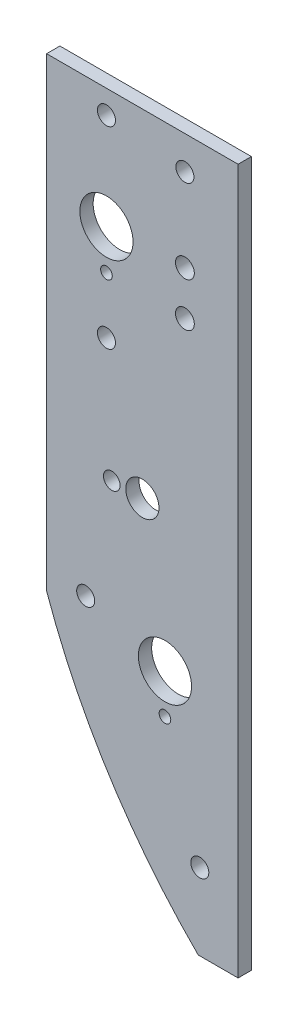
SolidWorks part; units mm, degrees
material "Acrylic (Medium-high impact)"
ref_plane "Front Plane" through (0, 0, 0) normal (0, 0, 1) x (1, 0, 0)
ref_plane "Top Plane" through (0, 0, 0) normal (0, 1, 0) x (1, 0, 0)
ref_plane "Right Plane" through (0, 0, 0) normal (1, 0, 0) x (0, 0, -1)
sketch "Sketch1" plane through (0, 0, 0) normal (0, 0, 1) x (1, 0, 0)
  line L4 (-45.72, 26.9875) -> (-45.72, -84.1375)
  line L5 (-9.525, -141.2875) -> (0, -141.2875)
  line L6 (0, -141.2875) -> (0, 26.9875)
  line L7 (0, 26.9875) -> (-45.72, 26.9875)
  line L8 (-45.72, 26.9875) -> (-45.72, -84.1375)
  line L9 (-9.525, -141.2875) -> (0, -141.2875)
  line L10 (0, -141.2875) -> (0, 26.9875)
  line L11 (0, 26.9875) -> (-45.72, 26.9875)
  arc A1 (-45.72, -84.1375) -> (-9.525, -141.2875) centre (97.9169, -33.2042) ccw
  arc A2 (-45.72, -84.1375) -> (-9.525, -141.2875) centre (97.9169, -33.2042) ccw
  dimension "D1" = 0
extrude "Boss-Extrude1" add sketch "Sketch1" against normal blind 3.175
hole_wizard "1/2 (0.5) Diameter Hole1" positions "Sketch4" profile "Sketch3" hole size "1/2" standard "ANSI Inch" end condition through all
sketch "Sketch4" plane through (0, 0, 0) normal (0, 0, 1) x (1, 0, 0)
  point P0 (-17.4625, -86.5505)
  point P4 (-31.4325, -1.6203)
sketch "Sketch3" plane through (-17.4625, -86.5505, 0) normal (1, 0, 0) x (0, -1, 0)
  line L0 (0, 0) -> (0, 3.175)
  line L1 (0, 3.175) -> (6.35, 3.175)
  line L2 (6.35, 3.175) -> (6.35, 0)
  line L5 (6.35, 0) -> (0, 0)
  line L11 (0, -6.35) -> (0, 107.95) construction
  dimension "Thru Hole Dia." = 12.7
  dimension "Thru Hole Depth" = 3.175
hole_wizard "5/16 (0.3125) Diameter Hole1" positions "Sketch6" profile "Sketch5" hole size "5/16" standard "ANSI Inch" end condition through all
sketch "Sketch6" plane through (0, 0, 0) normal (0, 0, 1) x (1, 0, 0)
  point P0 (-22.86, -53.5305)
sketch "Sketch5" plane through (-22.86, -53.5305, 0) normal (1, 0, 0) x (0, -1, 0)
  line L0 (0, 0) -> (0, 3.175)
  line L1 (0, 3.175) -> (3.9687, 3.175)
  line L2 (3.9687, 3.175) -> (3.9687, 0)
  line L5 (3.9687, 0) -> (0, 0)
  line L11 (0, -6.35) -> (0, 107.95) construction
  dimension "Thru Hole Dia." = 7.9375
  dimension "Thru Hole Depth" = 3.175
hole_wizard "5/32 (0.15625) Diameter Hole1" positions "Sketch8" profile "Sketch7" hole size "5/32" standard "ANSI Inch" end condition through all
sketch "Sketch8" plane through (0, 0, 0) normal (0, 0, 1) x (1, 0, 0)
  line L0 (-22.86, -49.5617) -> (-22.86, -53.5305) construction
  circle A0 centre (-22.86, -53.5305) radius 3.9688 construction
  point P11 (-30.1611, -53.5305)
sketch "Sketch7" plane through (-30.1611, -53.5305, 0) normal (1, 0, 0) x (0, -1, 0)
  line L0 (0, 0) -> (0, 3.175)
  line L1 (0, 3.175) -> (1.9844, 3.175)
  line L2 (1.9844, 3.175) -> (1.9844, 0)
  line L5 (1.9844, 0) -> (0, 0)
  line L11 (0, -6.35) -> (0, 107.95) construction
  dimension "Thru Hole Dia." = 3.9688
  dimension "Thru Hole Depth" = 3.175
hole_wizard "7/64 (0.10938) Diameter Hole1" positions "Sketch10" profile "Sketch9" hole size "7/64" standard "ANSI Inch" end condition through all
sketch "Sketch10" plane through (0, 0, 0) normal (0, 0, 1) x (1, 0, 0)
  point P0 (-17.4646, -95.9667)
  point P3 (-31.4325, -11.1589)
sketch "Sketch9" plane through (-17.4646, -95.9667, 0) normal (1, 0, 0) x (0, -1, 0)
  line L0 (0, 0) -> (0, 3.175)
  line L1 (0, 3.175) -> (1.3891, 3.175)
  line L2 (1.3891, 3.175) -> (1.3891, 0)
  line L5 (1.3891, 0) -> (0, 0)
  line L11 (0, -6.35) -> (0, 107.95) construction
  dimension "Thru Hole Dia." = 2.7783
  dimension "Thru Hole Depth" = 3.175
sketch "Sketch11" plane through (0, 0, -3.175) normal (0, 0, -1) x (-1, 0, 0)
  line L5 (19.8437, -15.24) -> (19.8437, 3.175)
  line L6 (19.8437, 3.175) -> (8.7312, 3.175)
  line L7 (8.7312, 3.175) -> (8.7312, -15.24)
  line L8 (8.7312, -15.24) -> (19.8437, -15.24)
  line L9 (19.8437, -15.24) -> (19.8437, 3.175)
  line L10 (19.8437, 3.175) -> (8.7312, 3.175)
  line L11 (8.7312, 3.175) -> (8.7312, -15.24)
  line L12 (8.7312, -15.24) -> (19.8437, -15.24)
  dimension "D1" = 0
extrude "Cut-Extrude4" [suppressed] cut sketch "Sketch11" against normal through all
hole_wizard "#6 Clearance Hole1" positions "Sketch13" profile "Sketch12" hole size "#6" standard "ANSI Inch" end condition through all
sketch "Sketch13" plane through (0, 0, -3.175) normal (0, 0, -1) x (-1, 0, 0)
  point P0 (12.7, 19.05)
  point P3 (36.3855, -80.4545)
  point P6 (9.144, -122.9995)
  point P10 (31.4325, -24.62)
  point P13 (31.4325, 21.4048)
sketch "Sketch12" plane through (-12.7, 19.05, -3.175) normal (1, 0, 0) x (0, 1, 0)
  line L0 (0, 0) -> (0, 3.175)
  line L1 (0, 3.175) -> (2.1526, 3.175)
  line L2 (2.1526, 3.175) -> (2.1526, 0)
  line L5 (2.1526, 0) -> (0, 0)
  line L11 (0, -6.35) -> (0, 107.95) construction
  dimension "Thru Hole Dia." = 4.3053
  dimension "Thru Hole Depth" = 3.175
hole_wizard "#16 (0.177) Diameter Hole1" positions "Sketch15" profile "Sketch14" hole size "#16" standard "ANSI Inch" end condition through all
sketch "Sketch15" plane through (0, 0, -3.175) normal (0, 0, -1) x (-1, 0, 0)
  line L5 (12.7, 2.794) -> (12.7, -14.859) construction
  line L6 (12.7, -6.0325) -> (17.8753, -6.0325) construction
  point P26 (12.7, -0.7804)
  point P33 (12.7, -11.2846)
sketch "Sketch14" plane through (-12.7, -0.7804, -3.175) normal (1, 0, 0) x (0, 1, 0)
  line L0 (0, 0) -> (0, 3.175)
  line L1 (0, 3.175) -> (2.2479, 3.175)
  line L2 (2.2479, 3.175) -> (2.2479, 0)
  line L5 (2.2479, 0) -> (0, 0)
  line L11 (0, -6.35) -> (0, 107.95) construction
  dimension "Thru Hole Dia." = 4.4958
  dimension "Thru Hole Depth" = 3.175
